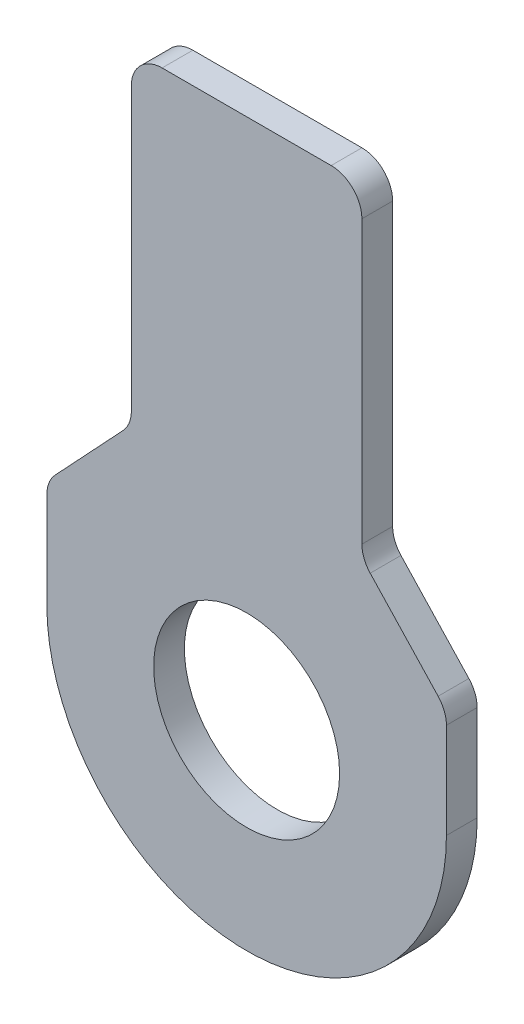
SolidWorks part; units mm, degrees
ref_plane "Front Plane" through (0, 0, 0) normal (0, 0, 1) x (1, 0, 0)
ref_plane "Top Plane" through (0, 0, 0) normal (0, 1, 0) x (1, 0, 0)
ref_plane "Right Plane" through (0, 0, 0) normal (1, 0, 0) x (0, 0, -1)
sketch "Sketch1" plane through (0, 0, 0) normal (0, 0, 1) x (1, 0, 0)
  line L0 (6.5, 0) -> (6.5, 3.105)
  line L1 (2.75, 17) -> (-2.75, 17)
  line L2 (-6.5, 3.105) -> (-6.5, 0)
  line L3 (6.2301, 3.7884) -> (4.0199, 6.15)
  line L5 (-4.0199, 6.15) -> (-6.2301, 3.7884)
  line L6 (3.75, 6.8333) -> (3.75, 16)
  line L8 (-3.75, 6.8333) -> (-3.75, 16)
  circle A0 centre (0, 0) radius 3.025
  arc A1 (-6.5, 0) -> (6.5, 0) centre (0, 0) ccw
  arc A2 (-3.75, 16) -> (-2.75, 17) centre (-2.75, 16) cw
  arc A3 (2.75, 17) -> (3.75, 16) centre (2.75, 16) cw
  arc A4 (-6.2301, 3.7884) -> (-6.5, 3.105) centre (-5.5, 3.105) ccw
  arc A5 (6.2301, 3.7884) -> (6.5, 3.105) centre (5.5, 3.105) cw
  arc A6 (4.0199, 6.15) -> (3.75, 6.8333) centre (4.75, 6.8333) cw
  arc A7 (-3.75, 6.8333) -> (-4.0199, 6.15) centre (-4.75, 6.8333) cw
  point P17 (-6.5, 3.5)
  point P20 (6.5, 3.5)
  point P23 (3.75, 6.4384)
  point P26 (-3.75, 6.4384)
  dimension "D1" = 6.05
  dimension "D2" = 6.5
  dimension "D3" = 1
  dimension "D4" = 17
  dimension "D5" = 7.5
  dimension "D6" = 3.5
  dimension "D7" = 6.8333
base flange "Base-Flange1" sketch "Sketch1" thickness 1 reverse thickness direction no parameters "D1"=2
sketch "Bend-Lines1" [suppressed] plane through (0, 0, 0) normal (0, 1, 0) x (1, 0, 0)
sketch "Bounding-Box1" [suppressed] plane through (0, 0, 0) normal (0, 1, 0) x (1, 0, 0)
sheet metal parameters "Sheet-Metal1" thickness 1 parameters "D1"=2
flat pattern "Flat-Pattern1" [suppressed]
sketch "Bend-Lines2" plane through (0, 0, 0) normal (0, 1, 0) x (1, 0, 0)
sketch3d "Bounding-Box2" [suppressed]
  line L0 (6.5, 17, 0) -> (6.5, -6.5, 0) construction
  line L1 (-6.5, 17, 0) -> (-6.5, -6.5, 0) construction
  line L2 (6.5, 17, 0) -> (-6.5, 17, 0) construction
  line L3 (6.5, -6.5, 0) -> (-6.5, -6.5, 0) construction
